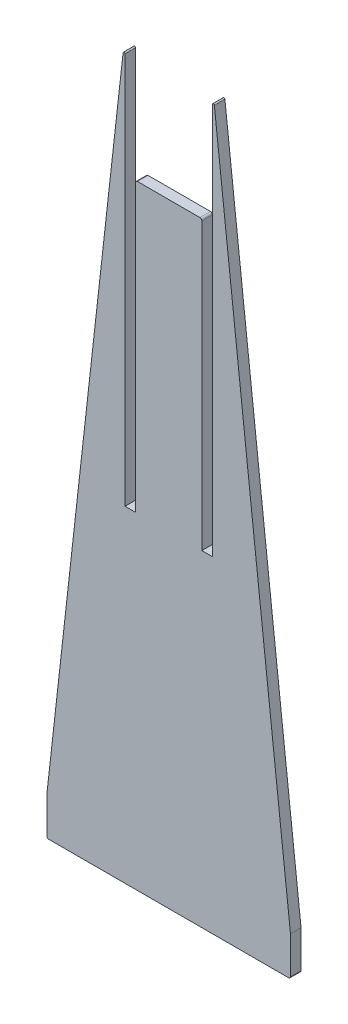
SolidWorks part; units mm, degrees
ref_plane "Front Plane" through (0, 0, 0) normal (0, 0, 1) x (1, 0, 0)
ref_plane "Top Plane" through (0, 0, 0) normal (0, 1, 0) x (1, 0, 0)
ref_plane "Right Plane" through (0, 0, 0) normal (1, 0, 0) x (0, 0, -1)
sketch "Sketch1" plane through (0, 0, 0) normal (0, 0, 1) x (1, 0, 0)
  line L0 (17.35, 0) -> (17.35, 20)
  line L1 (17.35, 0) -> (17.35, 20)
  line L2 (17.35, 20) -> (17.35, 195)
  line L3 (17.35, 20) -> (17.35, 195)
  line L4 (13.75, 450.8) -> (-13.75, 450.8)
  line L5 (-15.75, 448.8) -> (-15.75, 331.2)
  line L6 (-13.75, 329.2) -> (13.75, 329.2)
  line L7 (15.75, 331.2) -> (15.75, 448.8)
  line L8 (13.75, 450.8) -> (-13.75, 450.8)
  line L9 (-15.75, 448.8) -> (-15.75, 331.2)
  line L10 (-13.75, 329.2) -> (13.75, 329.2)
  line L11 (15.75, 331.2) -> (15.75, 448.8)
  line L12 (17.35, 195) -> (17.35, 390)
  line L13 (17.35, 195) -> (17.35, 390)
  line L14 (17.35, 390) -> (17.35, 406.6)
  line L15 (17.35, 390) -> (17.35, 406.6)
  line L16 (17.35, 406.6) -> (22.35, 406.6)
  line L17 (17.35, 406.6) -> (22.35, 406.6)
  line L18 (22.35, 406.6) -> (22.35, 390)
  line L19 (22.35, 406.6) -> (22.35, 390)
  line L20 (22.35, 390) -> (22.35, 195)
  line L21 (22.35, 390) -> (22.35, 195)
  line L22 (22.35, 195) -> (22.35, 20)
  line L23 (22.35, 195) -> (22.35, 20)
  line L24 (22.35, 20) -> (22.35, 0)
  line L25 (22.35, 20) -> (22.35, 0)
  line L26 (22.35, 0) -> (17.35, 0)
  line L28 (-22.35, 0) -> (-22.35, 20)
  line L29 (-22.35, 0) -> (-22.35, 20)
  line L30 (-22.35, 20) -> (-22.35, 195)
  line L31 (-22.35, 20) -> (-22.35, 195)
  line L32 (-22.35, 195) -> (-22.35, 390)
  line L33 (-22.35, 195) -> (-22.35, 390)
  line L34 (-22.35, 390) -> (-22.35, 406.6)
  line L35 (-22.35, 390) -> (-22.35, 406.6)
  line L36 (-22.35, 406.6) -> (-17.35, 406.6)
  line L37 (-22.35, 406.6) -> (-17.35, 406.6)
  line L38 (-17.35, 406.6) -> (-17.35, 390)
  line L39 (-17.35, 406.6) -> (-17.35, 390)
  line L40 (-17.35, 390) -> (-17.35, 195)
  line L41 (-17.35, 390) -> (-17.35, 195)
  line L42 (-17.35, 195) -> (-17.35, 20)
  line L43 (-17.35, 195) -> (-17.35, 20)
  line L44 (-17.35, 20) -> (-17.35, 0)
  line L45 (-17.35, 20) -> (-17.35, 0)
  line L46 (-17.35, 0) -> (-22.35, 0)
  line L47 (-17.35, 0) -> (-22.35, 0)
  line L48 (62.3, 20) -> (-62.3, 20) construction
  line L49 (62.3, 20) -> (-62.3, 20)
  line L50 (62.3, 0) -> (-62.3, 0) construction
  line L51 (62.3, 0) -> (-62.3, 0)
  line L52 (-75, 10.5) -> (-75, 0) construction
  line L53 (-75, 10.5) -> (-75, 0)
  line L54 (75, 0) -> (75, 10.5) construction
  line L55 (75, 0) -> (75, 10.5)
  line L56 (-16.25, 397.7) -> (-16.25, 382.3)
  line L57 (-16.25, 397.7) -> (-16.25, 382.3)
  line L58 (-16.25, 382.3) -> (-17.05, 381.5)
  line L59 (-16.25, 382.3) -> (-17.05, 381.5)
  line L60 (-17.05, 381.5) -> (-21.55, 381.5)
  line L61 (-17.05, 381.5) -> (-21.55, 381.5)
  line L62 (-21.55, 381.5) -> (-22.35, 382.3)
  line L63 (-21.55, 381.5) -> (-22.35, 382.3)
  line L64 (-22.35, 382.3) -> (-22.35, 397.7)
  line L65 (-22.35, 382.3) -> (-22.35, 397.7)
  line L66 (-22.35, 397.7) -> (-21.55, 398.5)
  line L67 (-22.35, 397.7) -> (-21.55, 398.5)
  line L68 (-21.55, 398.5) -> (-17.05, 398.5)
  line L69 (-21.55, 398.5) -> (-17.05, 398.5)
  line L70 (-17.05, 398.5) -> (-16.25, 397.7)
  line L71 (-17.05, 398.5) -> (-16.25, 397.7)
  line L72 (22.35, 397.7) -> (22.35, 382.3)
  line L73 (22.35, 397.7) -> (22.35, 382.3)
  line L74 (22.35, 382.3) -> (21.55, 381.5)
  line L75 (22.35, 382.3) -> (21.55, 381.5)
  line L76 (21.55, 381.5) -> (17.05, 381.5)
  line L77 (21.55, 381.5) -> (17.05, 381.5)
  line L78 (17.05, 381.5) -> (16.25, 382.3)
  line L79 (17.05, 381.5) -> (16.25, 382.3)
  line L80 (16.25, 382.3) -> (16.25, 397.7)
  line L81 (16.25, 382.3) -> (16.25, 397.7)
  line L82 (16.25, 397.7) -> (17.05, 398.5)
  line L83 (16.25, 397.7) -> (17.05, 398.5)
  line L84 (17.05, 398.5) -> (21.55, 398.5)
  line L85 (17.05, 398.5) -> (21.55, 398.5)
  line L86 (21.55, 398.5) -> (22.35, 397.7)
  line L87 (21.55, 398.5) -> (22.35, 397.7)
  line L100 (22.35, 0) -> (17.35, 0)
  arc A4 (-13.75, 450.8) -> (-15.75, 448.8) centre (-13.75, 448.8) ccw
  arc A5 (-15.75, 331.2) -> (-13.75, 329.2) centre (-13.75, 331.2) ccw
  arc A6 (13.75, 329.2) -> (15.75, 331.2) centre (13.75, 331.2) ccw
  arc A7 (15.75, 448.8) -> (13.75, 450.8) centre (13.75, 448.8) ccw
  arc A8 (-13.75, 450.8) -> (-15.75, 448.8) centre (-13.75, 448.8) ccw
  arc A9 (-15.75, 331.2) -> (-13.75, 329.2) centre (-13.75, 331.2) ccw
  arc A10 (13.75, 329.2) -> (15.75, 331.2) centre (13.75, 331.2) ccw
  arc A11 (15.75, 448.8) -> (13.75, 450.8) centre (13.75, 448.8) ccw
  dimension "D1" = 0
sketch "Sketch3" plane through (0, 0, 0) normal (0, 0, 1) x (1, 0, 0)
  line L0 (-22.35, 376.5) -> (-62.3, 20)
  line L1 (-22.35, 195) -> (-22.35, 390) construction
  line L2 (62.3, 20) -> (-62.3, 20) construction
  line L4 (-17.05, 381.5) -> (-21.55, 381.5) construction
  line L5 (-16.95, 314.2) -> (16.95, 314.2)
  line L8 (-13.75, 329.2) -> (13.75, 329.2) construction
  line L9 (-62.3, 20) -> (-62.3, 0)
  line L10 (62.3, 0) -> (-62.3, 0) construction
  line L11 (-62.3, 0) -> (62.3, 0)
  line L12 (-22.35, 376.5) -> (-22.35, 167.1)
  line L13 (-16.95, 314.2) -> (-16.95, 167.1)
  line L15 (16.95, 314.2) -> (16.95, 167.1)
  line L16 (0, 314.2) -> (0, 20) construction
  line L17 (-22.35, 167.1) -> (-16.95, 167.1)
  line L18 (22.35, 167.1) -> (16.95, 167.1)
  line L19 (22.35, 376.5) -> (22.35, 167.1)
  line L20 (22.35, 376.5) -> (62.3, 20)
  line L21 (62.3, 20) -> (62.3, 0)
  point P7 (22.35, 167.6451)
  point P13 (14.3485, 314.2)
  point P14 (0, 0)
  point P15 (0, 0)
  point P16 (17.35, 167.1)
  point P22 (0, 0)
  point P23 (0, 0)
  point P32 (0, 0)
  point P34 (0, 167.1)
  point P37 (17.35, 314.2)
  point P39 (0, 0)
  dimension "D1" = 5.4
  dimension "D2" = 5
  dimension "D3" = 15
extrude "Boss-Extrude1" add sketch "Sketch3" along normal mid plane 5.4
fillet "Fillet1" radius 1 4 edges at (-62.3, 0, 0) (62.3, 0, 0) (16.95, 314.2, 0) (-16.95, 314.2, 0)
fillet "Fillet2" radius 0.5 2 edges at (-22.35, 376.5, 0) (22.35, 376.5, 0)
equation "\"Black_acrylic\"= 1.35mm"
equation "\"MDF_base\"= 20mm"
equation "\"Supports_material\"= 5.4mm"
equation "\"D1@Boss-Extrude1\"=\"Supports_material\""
equation "\"D1@Sketch3\"=\"Supports_material\""
